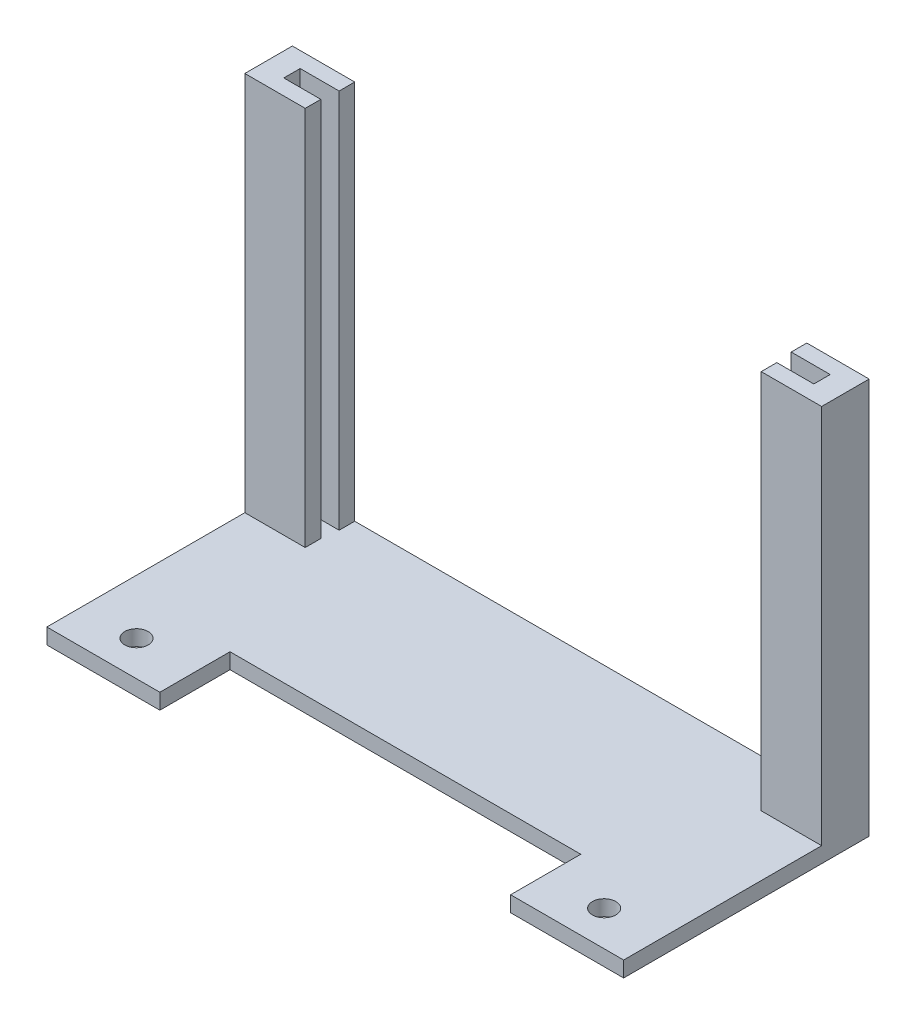
SolidWorks part; units mm, degrees
ref_plane "Front Plane" through (0, 0, 0) normal (0, 0, 1) x (1, 0, 0)
ref_plane "Top Plane" through (0, 0, 0) normal (0, 1, 0) x (1, 0, 0)
ref_plane "Right Plane" through (0, 0, 0) normal (1, 0, 0) x (0, 0, -1)
sketch "Sketch1" plane through (0, 0, 0) normal (0, 1, 0) x (1, 0, 0)
  line L0 (-29, 15.75) -> (-29, 13.75)
  line L1 (-37, 15.75) -> (37, 15.75)
  line L2 (-37, 15.75) -> (-37, -15.75)
  line L3 (-37, -15.75) -> (37, -15.75)
  line L4 (37, 15.75) -> (37, -15.75)
  line L5 (-37, 15.75) -> (37, -15.75) construction
  line L6 (-37, -15.75) -> (37, 15.75) construction
  line L7 (-29, 13.75) -> (-34, 13.75)
  line L8 (-34, 13.75) -> (-34, 11.65)
  line L9 (-34, 11.65) -> (-29.25, 11.65)
  line L10 (-29.25, 11.65) -> (-29.25, 9.65)
  line L11 (-29.25, 9.65) -> (-37, 9.65)
  line L12 (29, 15.75) -> (29, 13.75)
  line L13 (29, 13.75) -> (34, 13.75)
  line L14 (34, 13.75) -> (34, 11.65)
  line L15 (34, 11.65) -> (29.25, 11.65)
  line L16 (29.25, 11.65) -> (29.25, 9.65)
  line L17 (29.25, 9.65) -> (37, 9.65)
  line L18 (-30, -11.25) -> (30, -11.25) construction
  line L19 (-22.5, -6.75) -> (22.5, -6.75)
  line L20 (0, -6.75) -> (0, 0) construction
  line L21 (-22.5, -6.75) -> (-22.5, -15.75)
  line L22 (22.5, -6.75) -> (22.5, -15.75)
  circle A0 centre (-30, -11.25) radius 1.5
  circle A1 centre (30, -11.25) radius 1.5
  point P0 (0, 0)
  point P24 (0, -11.25)
  point P27 (-38.9518, -7.75)
  dimension "D5" = 3
  dimension "D1" = 2.1
  dimension "D2" = 68
  dimension "D3" = 58
  dimension "D4" = 2
  dimension "D6" = 60
  dimension "D7" = 25
  dimension "D8" = 4.5
  dimension "D9" = 9
  dimension "D10" = 45
  dimension "D11" = 3
  dimension "D12" = 58.5
extrude "Boss-Extrude1" add sketch "Sketch1" along normal blind 2 contours L19 L22 L3 L4 L17 L16 L15 L14 L13 L12 L1 L0 L7 L8 L9 L10 L11 L2 L21 A1 A0 | L11 L10 L9 L8 L7 L0 L1 L2 | L16 L17 L4 L1 L12 L13 L14 L15 region at (0, 0, -2.0439) region at (-29.1006, 0, -14.75) region at (33, 0, -15.6494)
extrude "Boss-Extrude2" add sketch "Sketch1<3>" along normal blind 50.8 contours L11 L10 L9 L8 L7 L0 L1 L2 | L16 L17 L4 L1 L12 L13 L14 L15 region at (-29.1006, 0, -14.75) region at (33, 0, -15.6494)
sketch "Sketch1<3>" plane through (0, 0, 0) normal (0, 1, 0) x (1, 0, 0) same geometry as "Sketch1"
